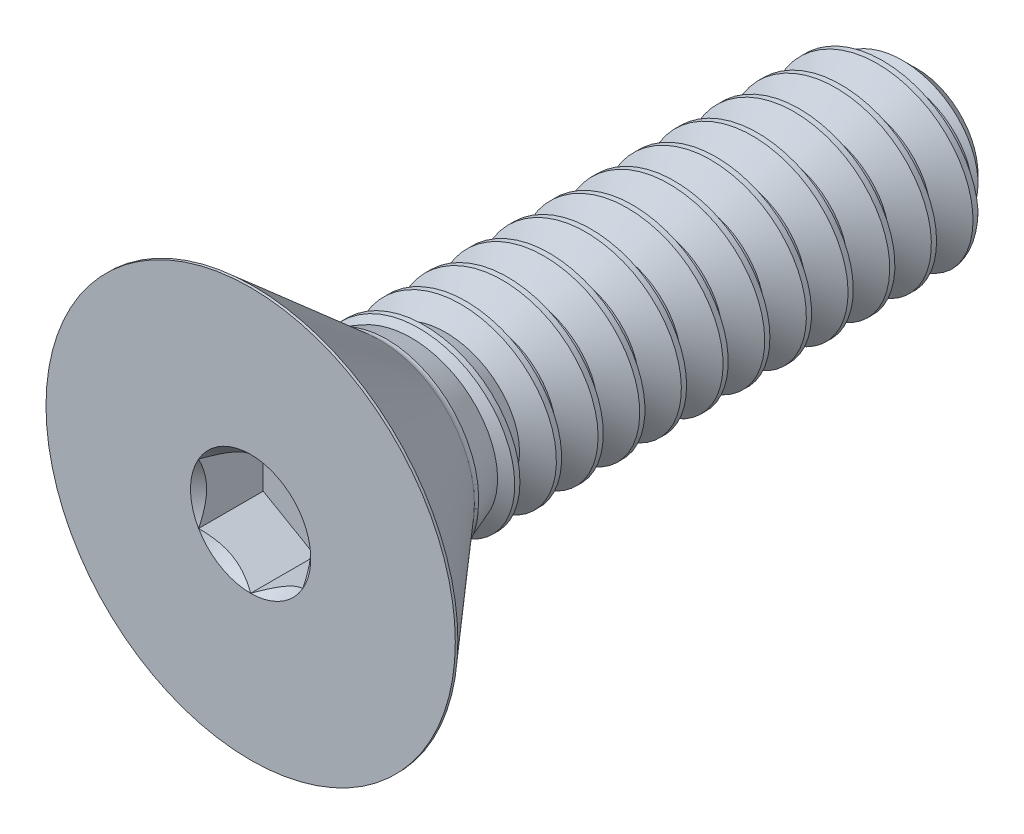
SolidWorks part; units mm, degrees
ref_plane "Front Plane" through (0, 0, 0) normal (0, 0, 1) x (1, 0, 0)
ref_plane "Top Plane" through (0, 0, 0) normal (0, 1, 0) x (1, 0, 0)
ref_plane "Right Plane" through (0, 0, 0) normal (1, 0, 0) x (0, 0, -1)
sketch "Sketch1" plane through (0, 0, 0) normal (1, 0, 0) x (0, 0, -1)
  line L0 (-6.35, 0) -> (6.35, 0) construction
  line L1 (-6.35, 0) -> (-6.35, 3.8989)
  line L2 (-6.35, 3.8989) -> (-6.3007, 3.8989)
  line L3 (-6.3007, 3.8989) -> (-3.8862, 1.8)
  line L4 (-6.3007, -3.8989) -> (-3.8862, -1.8)
  line L5 (6.35, 0) -> (6.35, 1.7526)
  line L6 (6.35, 1.7526) -> (-3.8862, 1.7526)
  line L7 (5.7547, 1.7526) -> (6.35, 1.1573)
  line L8 (6.3004, 1.8385) -> (6.6973, 1.1511) construction
  line L9 (6.6973, 1.1511) -> (7.0941, 1.8385) construction
  line L10 (7.0941, 1.8385) -> (6.3004, 1.8385) construction
  line L11 (6.3252, 1.7956) -> (7.0693, 1.7956)
  line L12 (7.0693, 1.7956) -> (6.7469, 1.237)
  line L13 (6.7469, 1.237) -> (6.6477, 1.237)
  line L14 (6.6477, 1.237) -> (6.3252, 1.7956)
  line L15 (6.6973, 1.237) -> (6.6973, 1.1511) construction
  line L16 (6.35, 1.7526) -> (7.0445, 1.7526) construction
  line L17 (6.6973, 1.8385) -> (6.6973, 1.7526) construction
  line L18 (6.35, -1.7526) -> (-3.8862, -1.7526)
  arc A0 (-3.8862, 1.8) -> (-3.7595, 1.7526) centre (-3.7595, 1.9458) ccw
  point P2 (0, 0)
  point P23 (-5.1181, 0)
  point P27 (6.6973, 1.7956)
  point P30 (5.1594, -1.7526)
  point P34 (-6.3007, -3.8989)
  dimension "Length" = 12.7
  dimension "Head Height" = 2.4638
  dimension "Head Diameter" = 7.7978
  dimension "Countersink Angle" = 82
  dimension "Thread Diameter" = 3.5052
  dimension "D2" = 0.0493
  dimension "Pitch" = 0.7937
  dimension "D4" = 0.0992
  dimension "D3" = 45
  dimension "D5" = 0.5953
  dimension "D6" = 1.2319
  dimension "D1" = 1.1906
sketch "Sketch2" plane through (0, 0, 0) normal (0, 0, 1) x (1, 0, 0)
  line L1 (0, 1.1457) -> (-0.9922, 0.5728)
  line L2 (-0.9922, 0.5728) -> (-0.9922, -0.5728)
  line L3 (-0.9922, -0.5728) -> (0, -1.1457)
  line L4 (0, -1.1457) -> (0.9922, -0.5728)
  line L5 (0.9922, -0.5728) -> (0.9922, 0.5728)
  line L6 (0.9922, 0.5728) -> (0, 1.1457)
  circle A0 centre (0, 0) radius 0.9922 construction
  dimension "Drive Size" = 1.9844
sketch "Sketch11" plane through (0, 0, 0) normal (1, 0, 0) x (0, 0, -1)
  line L0 (-6.3007, 3.8989) -> (-3.8862, 1.8) construction
  line L1 (-6.35, 0) -> (-6.35, 3.8989) construction
  line L2 (-6.3007, 3.8989) -> (-3.8862, 1.8)
  line L3 (-6.35, 0) -> (-6.35, 3.8989)
  line L4 (-6.35, 3.8989) -> (-6.3007, 3.8989) construction
  line L5 (-6.35, 3.8989) -> (-6.3007, 3.8989)
  line L6 (-3.7595, 1.7526) -> (5.7547, 1.7526)
  line L7 (5.7547, 1.7526) -> (6.35, 1.1573)
  line L8 (6.35, 1.1573) -> (6.35, 0)
  line L9 (6.35, 0) -> (-6.35, 0)
  arc A0 (-3.8862, 1.8) -> (-3.7595, 1.7526) centre (-3.7595, 1.9458) ccw construction
  arc A1 (-3.8862, 1.8) -> (-3.7595, 1.7526) centre (-3.7595, 1.9458) ccw
revolve "Revolve1" add sketch "Sketch11" angle 360 about L9
sketch "Sketch9" plane through (0, 0, 6.35) normal (0, 0, 1) x (1, 0, 0)
  line L0 (0.9922, -0.5728) -> (0.9922, 0.5728) construction
  line L1 (0, -1.1457) -> (0.9922, -0.5728) construction
  line L2 (-0.9922, -0.5728) -> (0, -1.1457) construction
  line L3 (-0.9922, 0.5728) -> (-0.9922, -0.5728) construction
  line L4 (0, 1.1457) -> (-0.9922, 0.5728) construction
  line L5 (0.9922, 0.5728) -> (0, 1.1457) construction
  line L6 (0.9922, -0.5728) -> (0.9922, 0.5728)
  line L7 (0, -1.1457) -> (0.9922, -0.5728)
  line L8 (-0.9922, -0.5728) -> (0, -1.1457)
  line L9 (-0.9922, 0.5728) -> (-0.9922, -0.5728)
  line L10 (0, 1.1457) -> (-0.9922, 0.5728)
  line L11 (0.9922, 0.5728) -> (0, 1.1457)
sketch "Sketch10" plane through (0, 0, 6.35) normal (0, 0, 1) x (1, 0, 0)
  circle A0 centre (0, 0) radius 1.1457
extrude "Cut-Extrude2" cut sketch "Sketch10" against normal up to vertex (1.2319 mm away) draft 45 up to point (0, 0, 5.1181)
extrude "Cut-Extrude1" cut sketch "Sketch9" against normal up to vertex (1.2319 mm away) up to point (0, 0, 5.1181)
ref_plane "Plane1" through (0, 0, 3.7595) normal (0, 0, 1) x (1, 0, 0)
split "Split1" trim tools "Plane1" bodies to split 111 resulting bodies 105 106
sketch "Sketch3" plane through (0, 0, -6.35) normal (0, 0, -1) x (-1, 0, 0)
  circle A0 centre (0, 0) radius 1.7526 construction
  circle A1 centre (0, 0) radius 1.7526
curve "Helix/Spiral1" pitch 0.7937 height 12.7 turns 16
sketch "Sketch4" plane through (0, 0, 0) normal (1, 0, 0) x (0, 0, -1)
  line L0 (6.3252, 1.7956) -> (7.0693, 1.7956) construction
  line L1 (6.6477, 1.237) -> (6.3252, 1.7956) construction
  line L2 (6.7469, 1.237) -> (6.6477, 1.237) construction
  line L3 (7.0693, 1.7956) -> (6.7469, 1.237) construction
  line L4 (6.3252, 1.7956) -> (7.0693, 1.7956)
  line L5 (6.6477, 1.237) -> (6.3252, 1.7956)
  line L6 (6.7469, 1.237) -> (6.6477, 1.237)
  line L7 (7.0693, 1.7956) -> (6.7469, 1.237)
sweep "Cut-Sweep1" cut profiles "Sketch4" path "Helix/Spiral1" align with end faces yes
sketch "Sketch7" plane through (0, 0, 3.7595) normal (0, 0, 1) x (1, 0, 0)
  circle A0 centre (0, 0) radius 1.7526
extrude "Boss-Extrude2" add sketch "Sketch7" against normal up to next (10.1095 mm away) draft 20
equation "\"D2@Sketch1\"=\"Head Height@Sketch1\"/50"
equation "\"D4@Sketch1\" = \"Pitch@Sketch1\" / 8"
equation "\"D5@Sketch1\"=\"Pitch@Sketch1\"*0.75"
equation "\"D4@Helix/Spiral1\"=\"Pitch@Sketch1\""
equation "\"D3@Helix/Spiral1\"=\"Length@Sketch1\""
equation "\"D6@Sketch1\"=\"Head Height@Sketch1\"/2"
equation "\"D1@Sketch1\"=\"Pitch@Sketch1\"*1.5"
